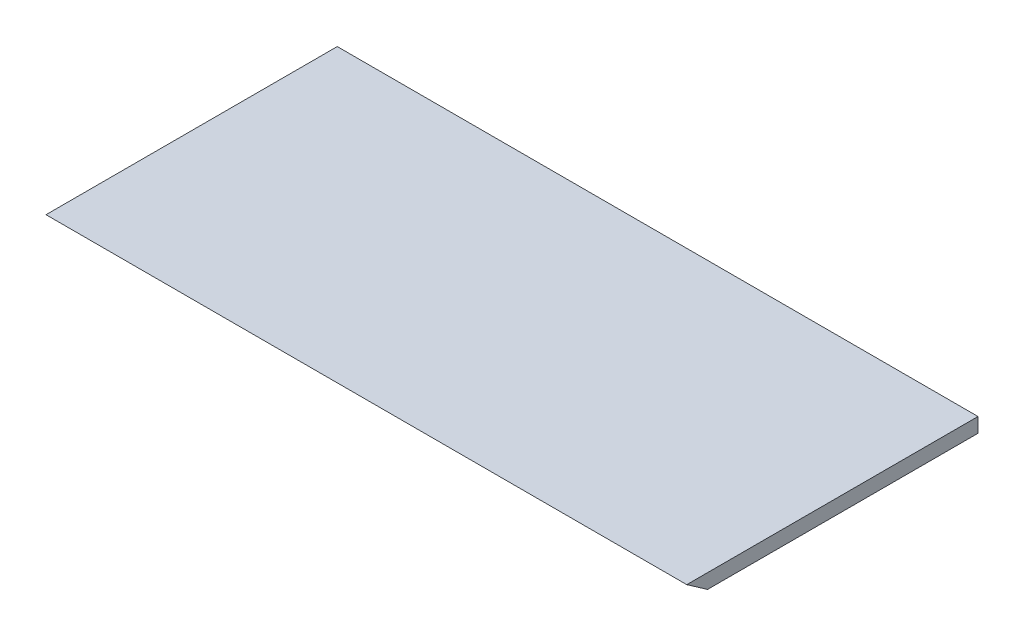
SolidWorks part; units mm, degrees
material "Ti-3Al-8V-6Cr-4Mo-4Zr (SS)"
ref_plane "Front Plane" through (0, 0, 0) normal (0, 0, 1) x (1, 0, 0)
ref_plane "Top Plane" through (0, 0, 0) normal (0, 1, 0) x (1, 0, 0)
ref_plane "Right Plane" through (0, 0, 0) normal (1, 0, 0) x (0, 0, -1)
sketch "Sketch1" plane through (0, 0, 0) normal (0, 1, 0) x (1, 0, 0)
  line L1 (69.85, -31.75) -> (-69.85, -31.75)
  line L2 (69.85, -31.75) -> (69.85, 31.75)
  line L3 (69.85, 31.75) -> (-69.85, 31.75)
  line L4 (-69.85, -31.75) -> (-69.85, 31.75)
  line L5 (69.85, -31.75) -> (-69.85, 31.75) construction
  line L6 (69.85, 31.75) -> (-69.85, -31.75) construction
  point P0 (0, 0)
  dimension "D1" = 139.7
  dimension "D2" = 63.5
extrude "Boss-Extrude1" add sketch "Sketch1" along normal blind 3.175
chamfer "Chamfer1" distance 3.175 angle 55 1 edges at (0, 0, 31.75) first distance on face at (0, 1.5875, 31.75)
